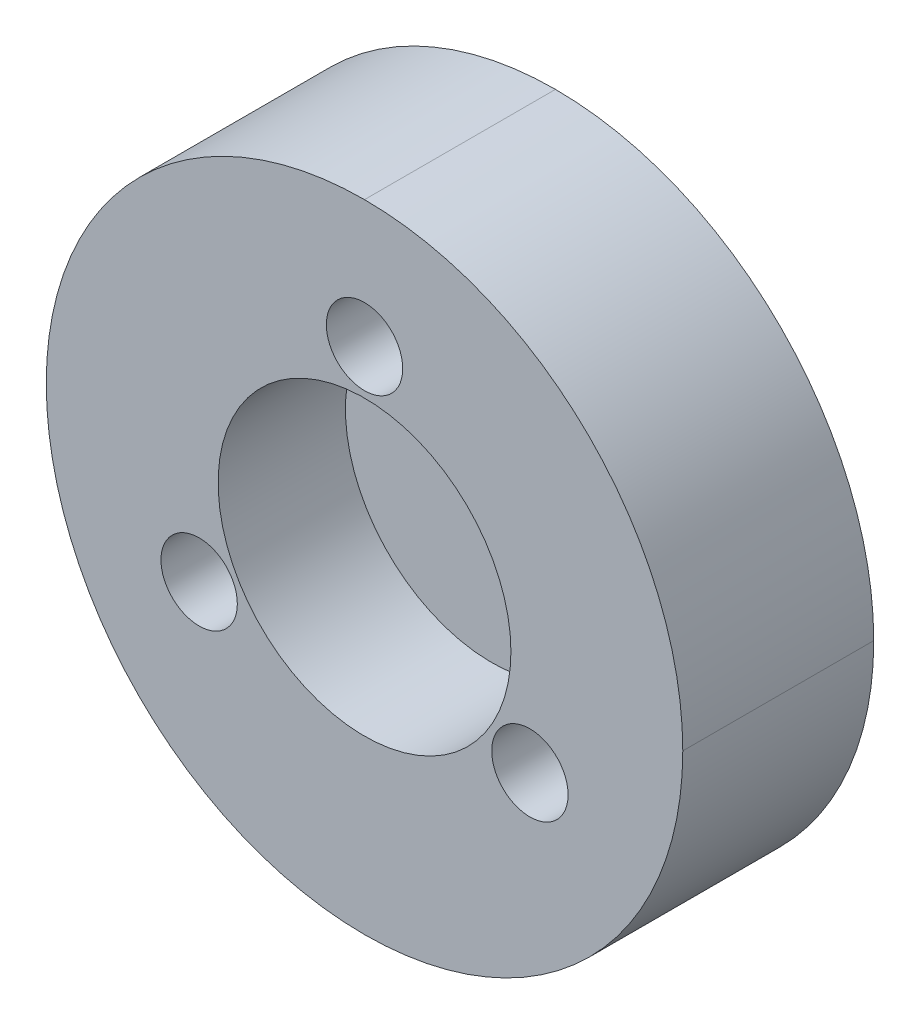
SolidWorks part; units mm, degrees
ref_plane "Front Plane" through (0, 0, 0) normal (0, 0, 1) x (1, 0, 0)
ref_plane "Top Plane" through (0, 0, 0) normal (0, 1, 0) x (1, 0, 0)
ref_plane "Right Plane" through (0, 0, 0) normal (1, 0, 0) x (0, 0, -1)
sketch "Sketch1" plane through (0, 0, 0) normal (0, 0, 1) x (1, 0, 0)
  line L0 (10, 10) -> (10, 16) construction
  line L1 (0, 0) -> (20, 0)
  line L2 (0, 0) -> (0, 20)
  line L3 (0, 20) -> (20, 20)
  line L4 (20, 0) -> (20, 20)
  line L5 (10, 10) -> (4.8038, 7) construction
  line L6 (10, 10) -> (15.1962, 7) construction
  circle A0 centre (10, 10) radius 6
  point P7 (10, 20)
  point P8 (0, 10)
  dimension "D2" = 12
  dimension "D1" = 20
  dimension "D3" = 120
  dimension "D4" = 120
extrude "Boss-Extrude1" add sketch "Sketch1" along normal blind 6 contours A0 | L1 L4 L3 L2 A0 region at (0.2828, 10, 0) region at (10, 10, 0)
hole_wizard "M2 Clearance Hole1" positions "Sketch2" profile "Sketch3" hole size "M2" standard "ANSI Metric"
sketch "Sketch2" plane through (0, 0, 6) normal (0, 0, 1) x (1, 0, 0)
  point P0 (10, 16)
  point P3 (15.1962, 7)
  point P6 (4.8038, 7)
sketch "Sketch3" plane through (10, 16, 6) normal (1, 0, 0) x (0, -1, 0)
  line L0 (0, 0) -> (0, 10.721)
  line L1 (0, 10.721) -> (1.2, 10)
  line L2 (1.2, 10) -> (1.2, 0)
  line L5 (1.2, 0) -> (0, 0)
  line L10 (0, 10.721) -> (-1.2, 10) construction
  line L11 (0, -6.35) -> (0, 107.95) construction
  dimension "Hole Dia." = 2.4
  dimension "Hole Depth" = 10
  dimension "Drill Angle" = 118
fillet "Fillet1" radius 10 4 edges at (0, 0, 3) (20, 0, 3) (20, 20, 3) (0, 20, 3)
sketch "Sketch4" plane through (0, 0, 6) normal (0, 0, 1) x (1, 0, 0)
  circle A0 centre (10, 10) radius 4.6
  dimension "D1" = 9.2
extrude "Cut-Extrude1" cut sketch "Sketch4" against normal blind 4
